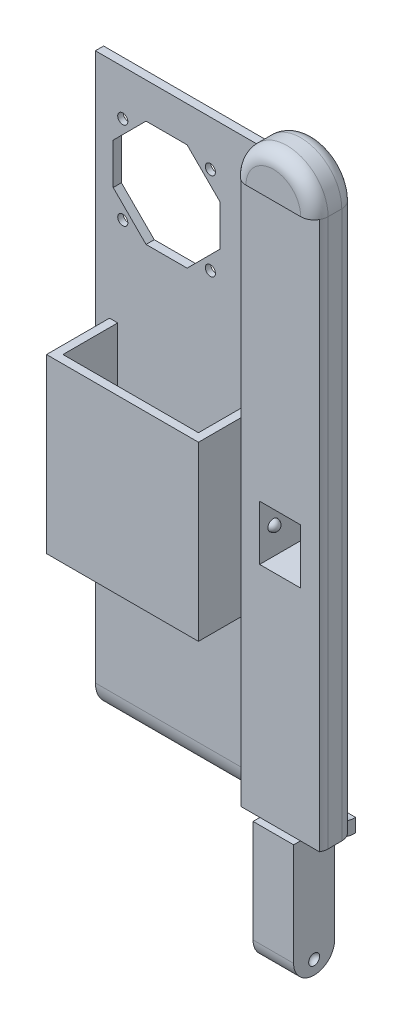
SolidWorks part; units mm, degrees
ref_plane "Front Plane" through (0, 0, 0) normal (0, 0, 1) x (1, 0, 0)
ref_plane "Top Plane" through (0, 0, 0) normal (0, 1, 0) x (1, 0, 0)
ref_plane "Right Plane" through (0, 0, 0) normal (1, 0, 0) x (0, 0, -1)
sketch "Sketch1" plane through (0, 0, 0) normal (0, 0, 1) x (1, 0, 0)
  line L0 (-15, 100) -> (-15, -100)
  line L1 (-15, -100) -> (-7.4, -100)
  line L2 (-7.4, -100) -> (-7.4, -150)
  line L3 (-7.4, -150) -> (7.4, -150)
  line L4 (7.4, -150) -> (7.4, -100)
  line L5 (7.4, -100) -> (15, -100)
  line L6 (15, -100) -> (15, 100)
  arc A0 (15, 100) -> (-15, 100) centre (0, 100) ccw
  dimension "D1" = 15
  dimension "D2" = 250
  dimension "D3" = 50
  dimension "D4" = 15
  dimension "D5" = 14.8
  dimension "D6" = 100
extrude "Boss-Extrude1" add sketch "Sketch1" along normal mid plane 15
fillet "Fillet1" radius 5 6 edges at (-15, 0, -7.5) (0, 115, -7.5) (-15, 0, 7.5) (0, 115, 7.5) (15, 0, -7.5) (15, 0, 7.5)
sketch "Sketch2" plane through (0, 0, 7.5) normal (0, 0, 1) x (1, 0, 0)
  line L0 (-10, 100) -> (-10, -100) construction
  line L1 (-7.5, 0) -> (7.5, 0)
  line L2 (-7.5, 0) -> (-7.5, -20)
  line L3 (-7.5, -20) -> (7.5, -20)
  line L4 (7.5, 0) -> (7.5, -20)
  dimension "D1" = 20
  dimension "D2" = 15
  dimension "D3" = 2.5
extrude "Cut-Extrude1" cut sketch "Sketch2" against normal through all
sketch "Sketch5" plane through (0, 0, 0) normal (0, 0, 1) x (1, 0, 0)
  line L0 (-35.5803, -140) -> (47.5468, -140) construction
  line L1 (-10, -100) -> (-7.4, -100) construction
  line L2 (-7.4, -140) -> (-5.4, -140)
  line L3 (-7.4, -100) -> (-7.4, -150) construction
  line L4 (-7.4, -138) -> (-7.4, -140)
  line L5 (7.4, -140) -> (5.4, -140)
  line L6 (7.4, -150) -> (7.4, -100) construction
  line L7 (7.4, -138) -> (7.4, -140)
  arc A0 (-5.4, -140) -> (-7.4, -138) centre (-7.4, -140) ccw
  arc A1 (5.4, -140) -> (7.4, -138) centre (7.4, -140) cw
  dimension "D1" = 40
  dimension "D2" = 2
  dimension "D3" = 2
revolve "Cut-Revolve1" cut sketch "Sketch5" angle 360 about L0
fillet "Fillet6" radius 5 2 edges at (-7.4, -150, 0) (7.4, -150, 0)
sketch "Sketch7" plane through (7.4, 0, 0) normal (1, 0, 0) x (0, 0, -1)
  line L0 (-7.5, -145) -> (-7.5, -100) construction
  line L1 (7.5, -145) -> (7.5, -100) construction
  line L2 (-7.5, -145) -> (7.5, -145) construction
  line L3 (-7.5, -137.5) -> (-7.5, -150)
  line L4 (-7.5, -150) -> (7.5, -150)
  line L5 (7.5, -150) -> (7.5, -137.5)
  arc A0 (-7.5, -137.5) -> (7.5, -137.5) centre (0, -137.5) ccw
extrude "Cut-Extrude2" cut sketch "Sketch7" against normal through all
sketch "Sketch9" plane through (0, 0, 0) normal (0, 0, 1) x (1, 0, 0)
  line L0 (-32.2513, -10) -> (37.8356, -10) construction
  line L1 (7.5, 0) -> (-7.5, 0) construction
  line L2 (-7.5, -10) -> (-5.5, -10)
  line L3 (-7.5, 0) -> (-7.5, -20) construction
  line L4 (-7.5, -8) -> (-7.5, -10)
  line L5 (7.5, -10) -> (5.5, -10)
  line L6 (7.5, -20) -> (7.5, 0) construction
  line L7 (7.5, -8) -> (7.5, -10)
  arc A0 (-5.5, -10) -> (-7.5, -8) centre (-7.5, -10) ccw
  arc A1 (5.5, -10) -> (7.5, -8) centre (7.5, -10) cw
  dimension "D1" = 10
  dimension "D2" = 2
  dimension "D3" = 2
revolve "Revolve2" add sketch "Sketch9" angle 360 about L0
sketch "Sketch10" plane through (0, 0, 0) normal (1, 0, 0) x (0, 0, -1)
  line L0 (7.5, -100) -> (7.5, 100)
  line L1 (7.5, 100) -> (10.5, 100)
  line L2 (10.5, 100) -> (10.5, -98.5193)
  line L3 (17.5, -105) -> (17.5, -110)
  arc A0 (10.5, -98.5193) -> (17.5, -105) centre (17, -98.5193) ccw
  arc A1 (17.5, -110) -> (7.5, -100) centre (17.5, -100) cw
  dimension "D2" = 10
  dimension "D4" = 6.5
  dimension "D1" = 5
  dimension "D3" = 3
  dimension "D5" = 10
extrude "Boss-Extrude2" add sketch "Sketch10" against normal blind 80
sketch "Sketch11" plane through (0, 0, 0) normal (1, 0, 0) x (0, 0, -1)
  line L0 (17.5, -110) -> (17.5, -105) construction
  line L1 (7.5, 100) -> (7.5, -100) construction
  line L2 (10.5, 100) -> (7.5, 100) construction
  line L3 (10.5, -98.5193) -> (10.5, 100) construction
  line L4 (17.5, -110) -> (17.5, -105)
  line L5 (7.5, 100) -> (7.5, -100)
  line L6 (10.5, 100) -> (7.5, 100)
  line L7 (10.5, -98.5193) -> (10.5, 100)
  arc A0 (10.5, -98.5193) -> (17.5, -105) centre (17, -98.5193) ccw construction
  arc A1 (7.5, -100) -> (17.5, -110) centre (17.5, -100) ccw construction
  arc A2 (10.5, -98.5193) -> (17.5, -105) centre (17, -98.5193) ccw
  arc A3 (7.5, -100) -> (17.5, -110) centre (17.5, -100) ccw
extrude "Boss-Extrude3" add sketch "Sketch11" along normal blind 5
sketch "Sketch12" plane through (0, 0, -10.5) normal (0, 0, -1) x (-1, 0, 0)
  line L0 (7.5, -20) -> (-5, -20) construction
  line L1 (7.5, -20) -> (-5, -20)
  line L2 (7.5, 0) -> (7.5, -20) construction
  line L3 (7.5, 0) -> (-5, 0) construction
  line L4 (80, 100) -> (-5, 100)
  line L5 (-5, 100) -> (-5, -98.5193)
  line L6 (-5, -98.5193) -> (80, -98.5193)
  line L7 (80, -98.5193) -> (80, 100)
  line L9 (-5, 0) -> (-5, -20)
  line L12 (7.5, 0) -> (7.5, -20)
  line L13 (7.5, 0) -> (-5, 0)
  dimension "D1" = 0
extrude "Cut-Extrude3" cut sketch "Sketch12" against normal blind 3
sketch "Sketch13" plane through (-15, 0, 0) normal (-1, 0, 0) x (0, 0, 1)
  line L0 (7.5, -100) -> (5, -100)
  line L1 (2.5, -100) -> (7.5, -100) construction
  line L2 (5, -100) -> (5, 100)
  line L3 (7.5, 100) -> (2.5, 100) construction
  line L4 (5, 100) -> (7.5, 100)
  line L5 (7.5, 100) -> (7.5, -100) construction
  line L6 (7.5, 100) -> (7.5, -100)
extrude "Cut-Extrude4" cut sketch "Sketch13" against normal through all
sketch "Sketch14" plane through (0, 0, -10.5) normal (0, 0, -1) x (-1, 0, 0)
  line L0 (80, -98.5193) -> (-5, -98.5193) construction
  line L1 (80, -98.5193) -> (80, 100) construction
  line L2 (61.5, 86.9807) -> (46.5, 86.9807)
  line L3 (46.5, 86.9807) -> (34.5, 74.9807)
  line L4 (34.5, 74.9807) -> (34.5, 59.9807)
  line L5 (34.5, 59.9807) -> (46.5, 47.9807)
  line L6 (46.5, 47.9807) -> (61.5, 47.9807)
  line L7 (61.5, 47.9807) -> (73.5, 59.9807)
  line L8 (73.5, 59.9807) -> (73.5, 74.9807)
  line L9 (73.5, 74.9807) -> (61.5, 86.9807)
  circle A0 centre (70, 51.4807) radius 1.85
  circle A1 centre (70, 83.4807) radius 1.85
  circle A2 centre (38, 83.4807) radius 1.85
  circle A3 centre (38, 51.4807) radius 1.85
  point P8 (54, 86.9807)
  point P21 (34.5, 67.4807)
  dimension "D4" = 3.7
  dimension "D1" = 150
  dimension "D2" = 32
  dimension "D3" = 32
  dimension "D5" = 10
  dimension "D6" = 15
  dimension "D7" = 16
  dimension "D8" = 16
  dimension "D9" = 39
extrude "Cut-Extrude5" cut sketch "Sketch14" against normal blind 10
sketch "Sketch15" plane through (0, 0, -10.5) normal (0, 0, -1) x (-1, 0, 0)
  circle A0 centre (70, 83.4807) radius 3.25
  circle A1 centre (38, 83.4807) radius 3.25
  circle A2 centre (38, 51.4807) radius 3.25
  circle A3 centre (70, 51.4807) radius 3.25
  dimension "D1" = 6.5
extrude "Cut-Extrude6" cut sketch "Sketch15" against normal blind 1
sketch "Sketch16" plane through (0, 100, 0) normal (0, 1, 0) x (1, 0, 0)
  line L0 (-80, 7.5) -> (-10, 7.5) construction
  line L2 (-71.85, 7.5) -> (-71.85, -12.5)
  line L3 (-71.85, -12.5) -> (-22.35, -12.5)
  line L4 (-22.35, 7.5) -> (-22.35, -12.5)
  line L5 (-71.85, -12.5) -> (-22.35, -12.5)
  line L7 (-74.85, -15.5) -> (-19.35, -15.5)
  line L10 (-71.85, -12.5) -> (-71.85, 7.5)
  line L12 (-74.85, -15.5) -> (-74.85, 7.5)
  line L13 (-74.85, 7.5) -> (-71.85, 7.5)
  line L15 (-22.35, -12.5) -> (-22.35, 7.5)
  line L17 (-19.35, -15.5) -> (-19.35, 7.5)
  line L18 (-22.35, 7.5) -> (-19.35, 7.5)
  line L19 (-74.85, 7.5) -> (-71.85, 7.5)
  line L20 (-22.35, 7.5) -> (-19.35, 7.5)
  line M21 (-80, 7.5) -> (-10, 7.5)
  dimension "D1" = 49.5
  dimension "D2" = 20
  dimension "D3" = 3
  dimension "D4" = 3
  dimension "D5" = 3
extrude "Boss-Extrude4" add sketch "Sketch16" against normal blind 170 contours L7 L17 L4 L3 L2 L12 M21 region at (-72.4508, 100, 2.5)
sketch "Sketch17" plane through (-74.85, 0, 0) normal (-1, 0, 0) x (0, 0, 1)
  line L0 (-7.5, 17.9807) -> (15.5, 17.9807)
  line L1 (-7.5, -70) -> (-7.5, 100) construction
  line L2 (15.5, -70) -> (15.5, 100) construction
  line L3 (-7.5, -42.0193) -> (15.5, -42.0193)
  line L4 (15.5, -42.0193) -> (15.5, -70)
  line L5 (15.5, -70) -> (-7.5, -70)
  line L6 (-7.5, -70) -> (-7.5, -42.0193)
  line L7 (-7.5, 17.9807) -> (-7.5, 100)
  line L8 (-7.5, 100) -> (15.5, 100)
  line L9 (15.5, 100) -> (15.5, 17.9807)
  dimension "D1" = 30
  dimension "D2" = 60
extrude "Cut-Extrude7" cut sketch "Sketch17" against normal blind 56
sketch "Sketch18" plane through (-74.85, 0, 0) normal (-1, 0, 0) x (0, 0, 1)
  line L0 (-7.5, 100) -> (-7.5, -100) construction
  line L1 (15.5, -42.0193) -> (-7.5, -42.0193)
  line L2 (15.5, -42.0193) -> (15.5, -45.0193)
  line L3 (15.5, -45.0193) -> (-7.5, -45.0193)
  line L4 (-7.5, -42.0193) -> (-7.5, -45.0193)
  dimension "D1" = 3
extrude "Boss-Extrude5" add sketch "Sketch18" against normal blind 55.5
